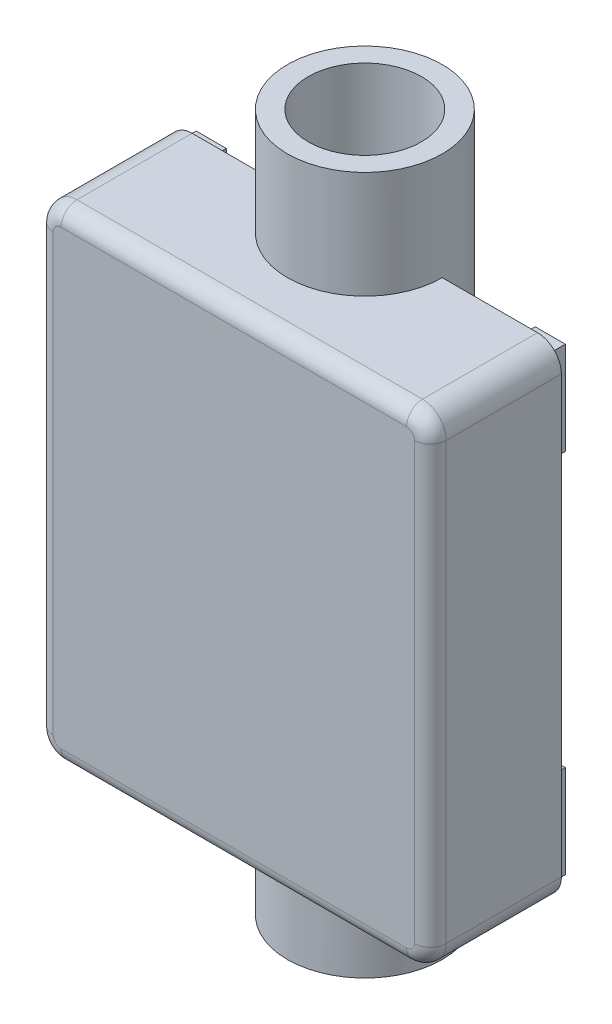
SolidWorks part; units mm, degrees
ref_plane "Front Plane" through (0, 0, 0) normal (1, 0, 0) x (0, 1, 0)
ref_plane "Top Plane" through (0, 0, 0) normal (0, 0, 1) x (0, 1, 0)
ref_plane "Right Plane" through (0, 0, 0) normal (0, 1, 0) x (-1, 0, 0)
sketch "Sketch1" plane through (0, 0, 0) normal (0, 0, 1) x (0, 1, 0)
  line L0 (-54.87, 46.5) -> (54.87, 46.5)
  line L1 (-54.87, 49.5) -> (54.87, 49.5)
  line L2 (-60.87, 43.5) -> (-60.87, -43.5)
  line L3 (-54.87, -49.5) -> (54.87, -49.5)
  line L4 (60.87, 43.5) -> (60.87, -43.5)
  line L5 (-60.87, 49.5) -> (60.87, -49.5) construction
  line L6 (-60.87, -49.5) -> (60.87, 49.5) construction
  line L7 (57.87, 43.5) -> (57.87, -43.5)
  line L8 (-54.87, -46.5) -> (54.87, -46.5)
  line L9 (-57.87, 43.5) -> (-57.87, -43.5)
  arc A0 (-54.87, -49.5) -> (-60.87, -43.5) centre (-54.87, -43.5) cw
  arc A1 (54.87, -49.5) -> (60.87, -43.5) centre (54.87, -43.5) ccw
  arc A2 (60.87, 43.5) -> (54.87, 49.5) centre (54.87, 43.5) ccw
  arc A3 (-60.87, 43.5) -> (-54.87, 49.5) centre (-54.87, 43.5) cw
  arc A4 (57.87, 43.5) -> (54.87, 46.5) centre (54.87, 43.5) ccw
  arc A5 (54.87, -46.5) -> (57.87, -43.5) centre (54.87, -43.5) ccw
  arc A6 (-54.87, -46.5) -> (-57.87, -43.5) centre (-54.87, -43.5) cw
  arc A7 (-57.87, 43.5) -> (-54.87, 46.5) centre (-54.87, 43.5) cw
  point P0 (0, 0)
  dimension "D3" = 6
  dimension "D1" = 121.74
  dimension "D2" = 99
  dimension "D4" = 3
extrude "Boss-Extrude1" add sketch "Sketch1" against normal blind 30
sketch "Sketch2" plane through (0, 0, 0) normal (0, 0, 1) x (1, 0, 0)
  line L0 (43.5, 60.87) -> (-43.5, 60.87) construction
  line L1 (-43.5, -60.87) -> (43.5, -60.87)
  line L2 (-49.5, -54.87) -> (-49.5, 54.87)
  line L3 (-43.5, 60.87) -> (43.5, 60.87)
  line L4 (49.5, -54.87) -> (49.5, 54.87)
  line L5 (-49.5, -60.87) -> (49.5, 60.87) construction
  line L6 (-49.5, 60.87) -> (49.5, -60.87) construction
  line L7 (49.5, -54.87) -> (49.5, 54.87) construction
  arc A0 (-43.5, -60.87) -> (-49.5, -54.87) centre (-43.5, -54.87) cw
  arc A1 (43.5, -60.87) -> (49.5, -54.87) centre (43.5, -54.87) ccw
  arc A2 (49.5, 54.87) -> (43.5, 60.87) centre (43.5, 54.87) ccw
  arc A3 (-49.5, 54.87) -> (-43.5, 60.87) centre (-43.5, 54.87) cw
  point P0 (0, 0)
  dimension "D1" = 6
extrude "Boss-Extrude2" add sketch "Sketch2" along normal blind 3
sketch "Sketch3" plane through (0, 60.87, 0) normal (0, 1, 0) x (-1, 0, 0)
  line L0 (0, -30) -> (0, 3) construction
  line L1 (-43.5, -30) -> (43.5, -30) construction
  line L2 (-43.5, 3) -> (43.5, 3) construction
  circle A0 centre (0, -30) radius 16.5
  dimension "D1" = 33
extrude "Cut-Extrude1" cut sketch "Sketch3" against normal blind 134
fillet "Fillet1" radius 4 1 edges at (0, -60.87, 3) type face fillet first side face at (0, -60.87, -16.25) second side face at (0, 0, 3)
sketch "Sketch4" plane through (0, 0, 0) normal (0, 0, -1) x (0, 1, 0)
  line L0 (-57.87, 16.5) -> (-57.87, 43.5) construction
  line L1 (-57.87, 30) -> (-46.8722, 30)
  line L2 (-57.87, 30) -> (-57.87, 43.5)
  line L3 (-54.87, 46.5) -> (-38.8722, 46.5)
  line L4 (-38.8722, 38) -> (-38.8722, 46.5)
  line L5 (-54.87, 46.5) -> (54.87, 46.5) construction
  line L6 (0, -46.5) -> (0, 46.5) construction
  line L7 (54.87, -46.5) -> (-54.87, -46.5) construction
  line L8 (-54.87, 46.5) -> (54.87, 46.5) construction
  line L9 (-60.87, 0) -> (60.87, 0) construction
  line L10 (-60.87, 16.5) -> (-60.87, -16.5) construction
  line L11 (60.87, -16.5) -> (60.87, 16.5) construction
  line L12 (38.8722, 38) -> (38.8722, 46.5)
  line L13 (54.87, 46.5) -> (38.8722, 46.5)
  line L14 (57.87, 30) -> (57.87, 43.5)
  line L15 (57.87, 30) -> (46.8722, 30)
  line L16 (57.87, -30) -> (46.8722, -30)
  line L17 (57.87, -30) -> (57.87, -43.5)
  line L18 (54.87, -46.5) -> (38.8722, -46.5)
  line L19 (38.8722, -38) -> (38.8722, -46.5)
  line L20 (-38.8722, -38) -> (-38.8722, -46.5)
  line L21 (-54.87, -46.5) -> (-38.8722, -46.5)
  line L22 (-57.87, -30) -> (-57.87, -43.5)
  line L23 (-57.87, -30) -> (-46.8722, -30)
  arc A0 (-54.87, 46.5) -> (-57.87, 43.5) centre (-54.87, 43.5) ccw
  arc A1 (-38.8722, 38) -> (-46.8722, 30) centre (-46.8722, 38) cw
  circle A2 centre (-46.8722, 38) radius 1.8
  circle A3 centre (46.8722, 38) radius 1.8
  arc A4 (38.8722, 38) -> (46.8722, 30) centre (46.8722, 38) ccw
  arc A5 (54.87, 46.5) -> (57.87, 43.5) centre (54.87, 43.5) cw
  arc A6 (54.87, -46.5) -> (57.87, -43.5) centre (54.87, -43.5) ccw
  arc A7 (38.8722, -38) -> (46.8722, -30) centre (46.8722, -38) cw
  circle A8 centre (46.8722, -38) radius 1.8
  circle A9 centre (-46.8722, -38) radius 1.8
  arc A10 (-38.8722, -38) -> (-46.8722, -30) centre (-46.8722, -38) ccw
  arc A11 (-54.87, -46.5) -> (-57.87, -43.5) centre (-54.87, -43.5) cw
  dimension "D1" = 3
  dimension "D2" = 8
  dimension "D3" = 3.6
extrude "Boss-Extrude3" [suppressed] add sketch "Sketch4" along normal blind 37
sketch "Sketch5" plane through (0, -57.87, 0) normal (0, 1, 0) x (-1, 0, 0)
  line L0 (-19.5, -30) -> (-16.5, -30)
  line L1 (16.5, -30) -> (19.5, -30)
  line L2 (-16.5, -30) -> (-43.5, -30) construction
  arc A0 (16.5, -30) -> (-16.5, -30) centre (0, -30) ccw
  arc A1 (19.5, -30) -> (-19.5, -30) centre (0, -30) ccw
  dimension "D1" = 3
extrude "Boss-Extrude4" add sketch "Sketch5" along normal blind 10 and the other way blind 10
fillet "Fillet2" radius 4 1 edges at (0, -57.87, -10.5)
fillet "Fillet3" [suppressed] radius 4
mirror "Mirror2" about plane through (0, 0, 0) normal (0, 1, 0) of "Boss-Extrude4"
fillet "Fillet4" [suppressed] radius 4
sketch "Sketch6" plane through (0, 0, 0) normal (0, 0, -1) x (1, 0, 0)
  line L0 (-43.5, 57.87) -> (-23.5, 57.87) construction
  line L1 (-46.5, 57.87) -> (-38.9, 57.87)
  line L2 (-46.5, 57.87) -> (-46.5, 34.48)
  line L3 (-46.5, 34.48) -> (-38.9, 34.48)
  line L4 (-38.9, 57.87) -> (-38.9, 34.48)
  line L5 (-46.5, -54.87) -> (-46.5, 54.87) construction
  line L6 (-42.7, 57.87) -> (-42.7, 34.48) construction
  line L7 (0, 67.87) -> (0, -67.87) construction
  line L8 (16.5, 67.87) -> (-16.5, 67.87) construction
  line L9 (-16.5, -67.87) -> (16.5, -67.87) construction
  line L10 (-49.5, 0) -> (49.5, 0) construction
  line L11 (-49.5, -54.87) -> (-49.5, 54.87) construction
  line L12 (49.5, 54.87) -> (49.5, -54.87) construction
  line L13 (46.5, 57.87) -> (38.9, 57.87)
  line L14 (38.9, 57.87) -> (38.9, 34.48)
  line L15 (46.5, 34.48) -> (38.9, 34.48)
  line L16 (46.5, 57.87) -> (46.5, 34.48)
  line L17 (-46.5, -34.48) -> (-38.9, -34.48)
  line L18 (-38.9, -57.87) -> (-38.9, -34.48)
  line L19 (-46.5, -57.87) -> (-38.9, -57.87)
  line L20 (-46.5, -57.87) -> (-46.5, -34.48)
  line L21 (46.5, -57.87) -> (46.5, -34.48)
  line L22 (46.5, -57.87) -> (38.9, -57.87)
  line L23 (38.9, -57.87) -> (38.9, -34.48)
  line L24 (46.5, -34.48) -> (38.9, -34.48)
  line L26 (40.5568, 56.3411) -> (44.7379, 56.3411)
  line L27 (40.5568, 56.3411) -> (40.5568, 49.1287)
  line L28 (40.5568, 49.1287) -> (44.7379, 49.1287)
  line L29 (44.7379, 56.3411) -> (44.7379, 49.1287)
  line L30 (40.5568, 42.4389) -> (44.7379, 42.4389)
  line L31 (40.5568, 42.4389) -> (40.5568, 36.0628)
  line L32 (40.5568, 36.0628) -> (44.7379, 36.0628)
  line L33 (44.7379, 42.4389) -> (44.7379, 36.0628)
  line L34 (-45.1556, 56.3411) -> (-40.3474, 56.3411)
  line L35 (-45.1556, 56.3411) -> (-45.1556, 49.1287)
  line L36 (-45.1556, 49.1287) -> (-40.3474, 49.1287)
  line L37 (-40.3474, 56.3411) -> (-40.3474, 49.1287)
  line L38 (-45.1556, 41.3937) -> (-40.3474, 41.3937)
  line L39 (-45.1556, 41.3937) -> (-45.1556, 36.0628)
  line L40 (-45.1556, 36.0628) -> (-40.3474, 36.0628)
  line L41 (-40.3474, 41.3937) -> (-40.3474, 36.0628)
  line L42 (-45.1556, -36.4793) -> (-40.3474, -36.4793)
  line L43 (-45.1556, -36.4793) -> (-45.1556, -42.8975)
  line L44 (-45.1556, -42.8975) -> (-40.3474, -42.8975)
  line L45 (-40.3474, -36.4793) -> (-40.3474, -42.8975)
  line L46 (-45.1556, -50.1325) -> (-40.3474, -50.1325)
  line L47 (-45.1556, -50.1325) -> (-45.1556, -56.6674)
  line L48 (-45.1556, -56.6674) -> (-40.3474, -56.6674)
  line L49 (-40.3474, -50.1325) -> (-40.3474, -56.6674)
  line L50 (40.5568, -36.4793) -> (44.7379, -36.4793)
  line L51 (40.5568, -36.4793) -> (40.5568, -42.8975)
  line L52 (40.5568, -42.8975) -> (44.7379, -42.8975)
  line L53 (44.7379, -36.4793) -> (44.7379, -42.8975)
  line L54 (40.5568, -50.1325) -> (44.7379, -50.1325)
  line L55 (40.5568, -50.1325) -> (40.5568, -56.6674)
  line L56 (40.5568, -56.6674) -> (44.7379, -56.6674)
  line L57 (44.7379, -50.1325) -> (44.7379, -56.6674)
  circle A0 centre (-42.7, 46.175) radius 1.8
  circle A1 centre (42.7, 46.175) radius 1.8
  circle A2 centre (-42.7, -46.175) radius 1.8
  circle A3 centre (42.7, -46.175) radius 1.8
  dimension "D3" = 3.6
  dimension "D1" = 23.39
  dimension "D2" = 7.6
extrude "Boss-Extrude5" add sketch "Sketch6" along normal blind 34
fillet "Fillet5" radius 7.5 1 edges at (-46.5, 34.48, -15)
fillet "Fillet6" radius 7.5 1 edges at (-46.5, -34.48, -15)
fillet "Fillet7" radius 7.5 1 edges at (46.5, -34.48, -15)
fillet "Fillet8" radius 7.5 1 edges at (46.5, 34.48, -15)
sketch "Sketch8" plane through (0, -47.87, 0) normal (0, 1, 0) x (-1, 0, 0)
  circle A0 centre (0, -30) radius 14.25
  circle A1 centre (0, -30) radius 19.5
  dimension "D1" = 28.5
extrude "Boss-Extrude6" add sketch "Sketch8" along normal up to surface (95.74 mm away) up to face at (0, 47.87, -21)
sketch "Sketch9" plane through (0, 0, 0) normal (0, 0, -1) x (1, 0, 0)
  line L0 (-46.5, 0) -> (46.5, 0) construction
  line L1 (-46.5, -26.98) -> (-46.5, 26.98) construction
  line L2 (46.5, 26.98) -> (46.5, -26.98) construction
  line L3 (0, 67.87) -> (0, -67.87) construction
  line L4 (-19.5, 13.5) -> (-46.5, 13.5)
  line L5 (-19.5, 13.5) -> (-19.5, -13.5)
  line L6 (-19.5, -13.5) -> (-46.5, -13.5)
  line L7 (-46.5, 13.5) -> (-46.5, -13.5)
  line L8 (-19.5, 13.5) -> (-46.5, -13.5) construction
  line L9 (-19.5, -13.5) -> (-46.5, 13.5) construction
  line L10 (16.5, 67.87) -> (-16.5, 67.87) construction
  line L11 (-16.5, -67.87) -> (16.5, -67.87) construction
  line L12 (19.5, -13.5) -> (46.5, 13.5) construction
  line L13 (19.5, 13.5) -> (46.5, -13.5) construction
  line L14 (46.5, 13.5) -> (46.5, -13.5)
  line L15 (19.5, -13.5) -> (46.5, -13.5)
  line L16 (19.5, 13.5) -> (19.5, -13.5)
  line L17 (19.5, 13.5) -> (46.5, 13.5)
  line L18 (-19.5, 47.87) -> (-19.5, -47.87) construction
  line L19 (-44.5, 11.5) -> (-21.5, 11.5)
  line L20 (-44.5, 11.5) -> (-44.5, -11.5)
  line L21 (-44.5, -11.5) -> (-21.5, -11.5)
  line L22 (-21.5, 11.5) -> (-21.5, -11.5)
  line L23 (-44.5, 11.5) -> (-21.5, -11.5) construction
  line L24 (-44.5, -11.5) -> (-21.5, 11.5) construction
  line L26 (44.6723, 11.6723) -> (21.3277, 11.6723)
  line L27 (44.6723, 11.6723) -> (44.6723, -11.6723)
  line L28 (44.6723, -11.6723) -> (21.3277, -11.6723)
  line L29 (21.3277, 11.6723) -> (21.3277, -11.6723)
  line L30 (44.6723, 11.6723) -> (21.3277, -11.6723) construction
  line L31 (44.6723, -11.6723) -> (21.3277, 11.6723) construction
  point P6 (-33, 0)
  point P21 (33, 0)
  point P22 (-33, 0)
  point P27 (21.3277, 11.6723)
  point P30 (33, 0)
  dimension "D1" = 2
  dimension "D2" = 2
extrude "Boss-Extrude7" [suppressed] add sketch "Sketch9" along normal blind 25.2
sketch "Sketch10" plane through (0, -47.87, 0) normal (0, -1, 0) x (1, 0, 0)
  circle A0 centre (0, -30) radius 19.5
  circle A1 centre (0, -30) radius 14.25
extrude "Boss-Extrude8" add sketch "Sketch10" along normal blind 40
sketch "Sketch11" plane through (0, 47.87, 0) normal (0, 1, 0) x (-1, 0, 0)
  circle A0 centre (0, -30) radius 19.5
  circle A1 centre (0, -30) radius 14.25
extrude "Boss-Extrude9" add sketch "Sketch11" along normal blind 40
sketch "Sketch12" plane through (0, 0, 0) normal (1, 0, 0) x (0, 1, 0)
  line L0 (-54.87, -29.9) -> (54.87, -29.9) construction
  line L3 (-54.87, -30) -> (54.87, -30) construction
  circle A0 centre (0, -29.9) radius 2.5
  circle A1 centre (-50, -29.9) radius 2.5
  circle A2 centre (50, -29.9) radius 2.5
  dimension "D1" = 5
  dimension "D5" = 5
  dimension "D6" = 5
  dimension "D2" = 0.1
  dimension "D3" = 50
  dimension "D4" = 50
extrude "Cut-Extrude2" cut sketch "Sketch12" against normal blind 26 and the other way blind 40
sketch "Sketch13" [suppressed] plane through (21.3277, 0, 0) normal (1, 0, 0) x (0, 1, 0)
  line L0 (0, -30) -> (0, -25.2)
  line L1 (26.98, -30) -> (-26.98, -30) construction
  dimension "D1" = 4.8
fillet "Fillet9" radius 4 1 edges at (0, 57.87, -10.5) type face fillet first side face at (-19.3593, -49.4484, -32.3384) second side face at (0, 57.87, -16.75)
sketch "Sketch14" plane through (0, 0, 0) normal (0, 0, -1) x (1, 0, 0)
  line L1 (10.2417, 33.7428) -> (-9.8759, 33.7428)
  line L2 (10.2417, 33.7428) -> (10.2417, -36.1204)
  line L3 (10.2417, -36.1204) -> (-9.8759, -36.1204)
  line L4 (-9.8759, 33.7428) -> (-9.8759, -36.1204)
  line L5 (6.584, 30.2679) -> (-6.0353, 30.2679)
  line L6 (6.584, 30.2679) -> (6.584, -31.3653)
  line L7 (6.584, -31.3653) -> (-6.0353, -31.3653)
  line L8 (-6.0353, 30.2679) -> (-6.0353, -31.3653)
extrude "Boss-Extrude10" add sketch "Sketch14" along normal blind 14.8
